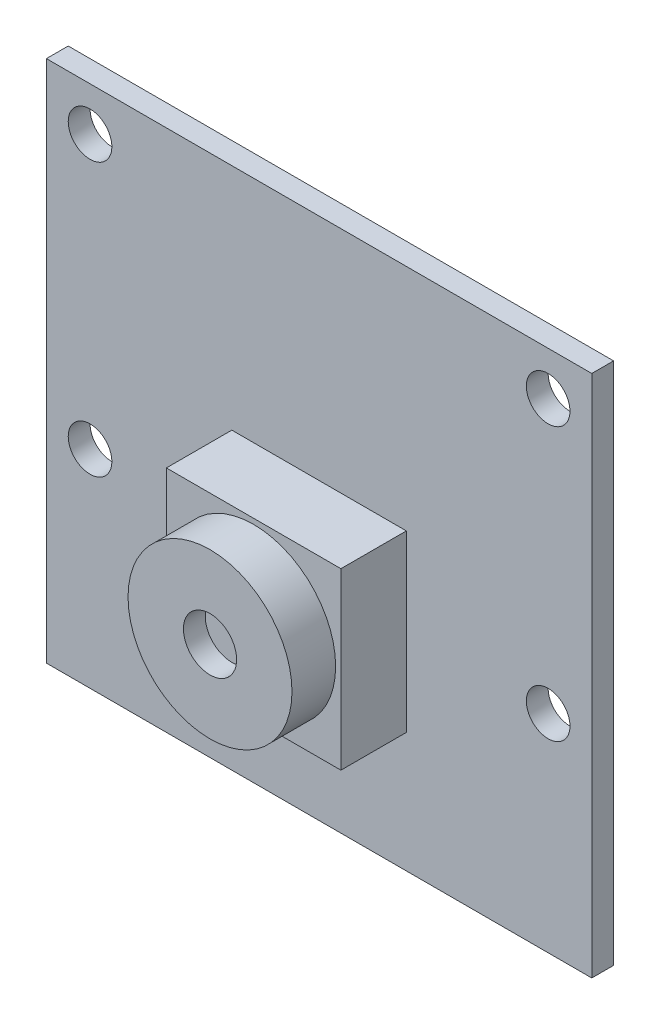
SolidWorks part; units mm, degrees
ref_plane "Front Plane" through (0, 0, 0) normal (0, 0, 1) x (1, 0, 0)
ref_plane "Top Plane" through (0, 0, 0) normal (0, 1, 0) x (1, 0, 0)
ref_plane "Right Plane" through (0, 0, 0) normal (1, 0, 0) x (0, 0, -1)
ref_axis "Axis1" through (-88.99, 0, 0) along (1, 0, 0)
ref_axis "Axis2" through (0, 55, 0) along (0, -1, 0)
ref_axis "Axis3" through (0, 0, 55) along (0, 0, -1)
ref_point "Point1"
sketch "Sketch1" plane through (0, 0, 0) normal (0, 0, 1) x (1, 0, 0)
  line L1 (-12.5, -12) -> (12.5, -12)
  line L2 (-12.5, -12) -> (-12.5, 12)
  line L3 (-12.5, 12) -> (12.5, 12)
  line L4 (12.5, -12) -> (12.5, 12)
  line L5 (-12.5, -12) -> (12.5, 12) construction
  line L6 (-12.5, 12) -> (12.5, -12) construction
  point P0 (0, 0)
  dimension "D1" = 25
  dimension "D2" = 24
extrude "Boss-Extrude1" add sketch "Sketch1" along normal blind 1
sketch "Sketch2" plane through (0, 0, 1) normal (0, 0, 1) x (1, 0, 0)
  line L0 (-12.5, -12) -> (12.5, -12) construction
  line L1 (-4, -6.5) -> (4, -6.5)
  line L2 (-4, -6.5) -> (-4, 1.5)
  line L3 (-4, 1.5) -> (4, 1.5)
  line L4 (4, -6.5) -> (4, 1.5)
  line L5 (-4, -6.5) -> (4, 1.5) construction
  line L6 (-4, 1.5) -> (4, -6.5) construction
  line L7 (-12.5, 12) -> (-12.5, -12) construction
  point P0 (0, -2.5)
  dimension "D1" = 8
  dimension "D2" = 5.5
  dimension "D3" = 8.5
extrude "Boss-Extrude2" add sketch "Sketch2" along normal blind 3 separate body
sketch "Sketch3" plane through (0, 0, 4) normal (0, 0, 1) x (1, 0, 0)
  line L0 (-4, -6.5) -> (4, 1.5) construction
  line L1 (4, -6.5) -> (4, 1.5) construction
  line L2 (4, 1.5) -> (-4, 1.5) construction
  circle A0 centre (0, -2.5) radius 3.7578
extrude "Boss-Extrude3" add sketch "Sketch3" along normal blind 2 separate body
sketch "Sketch4" plane through (0, 0, 6) normal (0, 0, 1) x (1, 0, 0)
  circle A0 centre (0, -2.5) radius 1.219
extrude "Cut-Extrude1" cut sketch "Sketch4" against normal blind 1
sketch "Sketch5" plane through (0, 0, 1) normal (0, 0, 1) x (1, 0, 0)
  line L0 (-12.5, -12) -> (12.5, -12) construction
  line L1 (-10.5, 10) -> (10.5, 10) construction
  line L2 (-10.5, 10) -> (-10.5, -2.5) construction
  line L3 (-10.5, -2.5) -> (10.5, -2.5) construction
  line L4 (10.5, 10) -> (10.5, -2.5) construction
  line L5 (-10.5, 10) -> (10.5, -2.5) construction
  line L6 (-10.5, -2.5) -> (10.5, 10) construction
  line L7 (12.5, 12) -> (-12.5, 12) construction
  line L8 (0, 10) -> (0, 12) construction
  line L9 (12.5, -12) -> (12.5, 12) construction
  circle A0 centre (-10.5, -2.5) radius 1
  circle A1 centre (-10.5, 10) radius 1
  circle A2 centre (10.5, 10) radius 1
  circle A3 centre (10.5, -2.5) radius 1
  point P0 (0, 3.75)
  dimension "D4" = 2
  dimension "D1" = 9.5
  dimension "D2" = 2
  dimension "D3" = 21
extrude "Cut-Extrude2" cut sketch "Sketch5" against normal through all both and the other way through all
